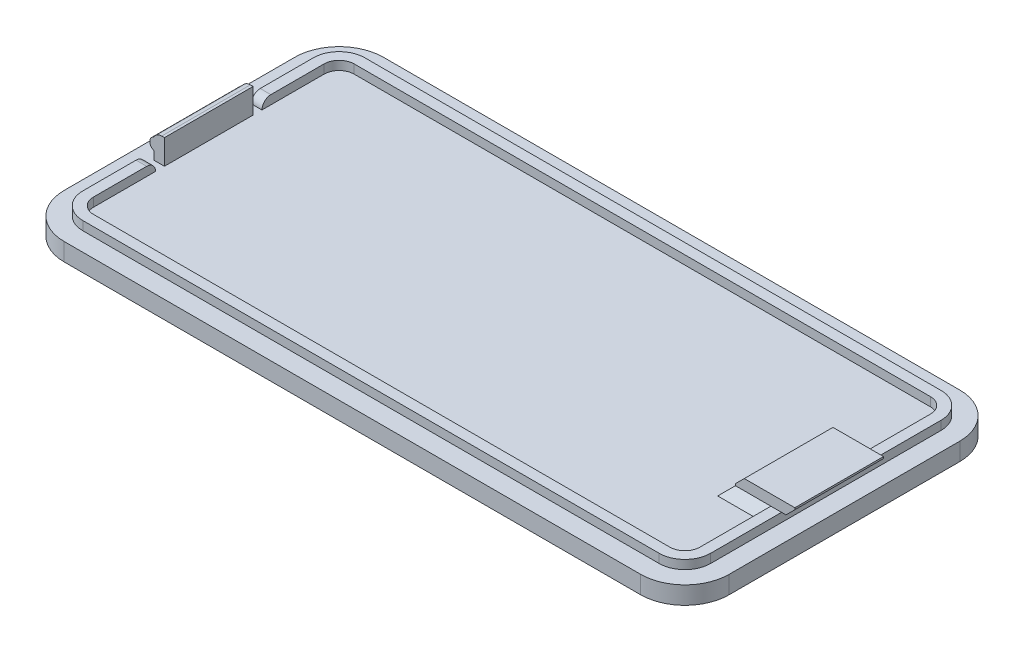
SolidWorks part; units mm, degrees
ref_plane "前视基准面" through (0, 0, 0) normal (0, 0, 1) x (1, 0, 0)
ref_plane "上视基准面" through (0, 0, 0) normal (0, 1, 0) x (1, 0, 0)
ref_plane "右视基准面" through (0, 0, 0) normal (1, 0, 0) x (0, 0, -1)
sketch "zero" plane through (0, 0, 0) normal (0, 1, 0) x (1, 0, 0)
  line L1 (-29.5, 15) -> (29.5, 15)
  line L2 (-32.5, 12) -> (-32.5, -12)
  line L3 (-29.5, -15) -> (29.5, -15)
  line L4 (32.5, 12) -> (32.5, -12)
  line L5 (-32.5, 15) -> (32.5, -15) construction
  line L6 (-32.5, -15) -> (32.5, 15) construction
  line L7 (-25.7, -15) -> (-14.5, -15)
  line L8 (-25.7, -15) -> (-25.7, -9.6569)
  line L9 (-25.7, -9.6569) -> (-14.5, -9.6569)
  line L10 (-14.5, -15) -> (-14.5, -9.6569)
  line L11 (5.2, -15) -> (12.7, -15)
  line L12 (5.2, -15) -> (5.2, -11)
  line L13 (5.2, -11) -> (12.7, -11)
  line L14 (12.7, -15) -> (12.7, -11)
  line L15 (17.8, -15) -> (25.3, -15)
  line L16 (17.8, -15) -> (17.8, -11)
  line L17 (17.8, -11) -> (25.3, -11)
  line L18 (25.3, -15) -> (25.3, -11)
  line L19 (-32.5, 7.7) -> (-19.5, 7.7)
  line L20 (-32.5, 7.7) -> (-32.5, -4.3)
  line L21 (-32.5, -4.3) -> (-19.5, -4.3)
  line L22 (-19.5, 7.7) -> (-19.5, -4.3)
  line L23 (-25.5, 14) -> (25.5, 14)
  line L24 (-25.5, 14) -> (-25.5, 8.8)
  line L25 (-25.5, 8.8) -> (25.5, 8.8)
  line L26 (25.5, 14) -> (25.5, 8.8)
  line L27 (-19.5, 7.2329) -> (-35.5, 7.2329)
  line L28 (-19.5, 7.2329) -> (-19.5, -3.7671)
  line L29 (-19.5, -3.7671) -> (-35.5, -3.7671)
  line L30 (-35.5, 7.2329) -> (-35.5, -3.7671)
  arc A0 (29.5, -15) -> (32.5, -12) centre (29.5, -12) ccw
  arc A1 (29.5, 15) -> (32.5, 12) centre (29.5, 12) cw
  arc A2 (-32.5, -12) -> (-29.5, -15) centre (-29.5, -12) ccw
  arc A3 (-29.5, 15) -> (-32.5, 12) centre (-29.5, 12) ccw
  circle A4 centre (-29, 11.4) radius 3
  circle A5 centre (-29, -11.5) radius 3
  circle A6 centre (29, 11.4) radius 3
  circle A7 centre (29, -11.5) radius 3
  circle A8 centre (-29, 11.4) radius 1.375
  circle A9 centre (-29, -11.5) radius 1.375
  circle A10 centre (29, -11.5) radius 1.375
  circle A11 centre (29, 11.4) radius 1.375
  point P0 (0, 0)
  dimension "D3" = 3
  dimension "D4" = 6
  dimension "D9" = 2.75
  dimension "D1" = 65
  dimension "D2" = 30
  dimension "D5" = 3.6
  dimension "D6" = 3.5
  dimension "D7" = 3.5
  dimension "D8" = 3.5
  dimension "D10" = 12
  dimension "D11" = 7.3
  dimension "D12" = 13
  dimension "D13" = 11.2
  dimension "D14" = 6.8
  dimension "D15" = 19.7
  dimension "D16" = 7.5
  dimension "D17" = 7.5
  dimension "D18" = 5.1
  dimension "D19" = 4
  dimension "D20" = 5.2
  dimension "D21" = 7
  dimension "D22" = 7
  dimension "D23" = 1
  dimension "D24" = 11
  dimension "D25" = 16
sketch "sugar" plane through (0, 0, 0) normal (0, 1, 0) x (1, 0, 0)
  line L1 (-29.5, 15) -> (29.5, 15)
  line L2 (-32.5, 12) -> (-32.5, -12)
  line L3 (-29.5, -15) -> (29.5, -15)
  line L4 (32.5, 12) -> (32.5, -12)
  line L5 (-32.5, 15) -> (32.5, -15) construction
  line L6 (-32.5, -15) -> (32.5, 15) construction
  line L7 (23.5, -11.5) -> (19.5, -11.5)
  line L8 (23.5, -11.5) -> (23.5, -13.9082)
  line L9 (23.5, -13.9082) -> (19.5, -13.9082)
  line L10 (19.5, -11.5) -> (19.5, -13.9082)
  line L11 (16, -11.0071) -> (8.5, -11.0071)
  line L12 (16, -11.0071) -> (16, -15)
  line L13 (16, -15) -> (8.5, -15)
  line L14 (8.5, -11.0071) -> (8.5, -15)
  line L15 (20.5, -13.9082) -> (22.5, -13.9082)
  line L16 (20.5, -13.9082) -> (20.5, -14.8173)
  line L17 (20.5, -14.8173) -> (22.5, -14.8173)
  line L18 (22.5, -13.9082) -> (22.5, -14.8173)
  arc A0 (29.5, 15) -> (32.5, 12) centre (29.5, 12) cw
  arc A1 (29.5, -15) -> (32.5, -12) centre (29.5, -12) ccw
  arc A2 (-32.5, -12) -> (-29.5, -15) centre (-29.5, -12) ccw
  arc A3 (-29.5, 15) -> (-32.5, 12) centre (-29.5, 12) ccw
  circle A4 centre (-29, 11.4) radius 3
  circle A5 centre (-29, 11.4) radius 1.375
  circle A6 centre (-29, -11.5) radius 3
  circle A7 centre (-29, -11.5) radius 1.375
  circle A8 centre (29, 11.4) radius 3
  circle A9 centre (29, 11.4) radius 1.375
  circle A10 centre (29, -11.5) radius 3
  circle A11 centre (29, -11.5) radius 1.375
  dimension "D3" = 3
  dimension "D1" = 65
  dimension "D2" = 30
  dimension "D4" = 9
  dimension "D5" = 4
  dimension "D6" = 3.5
  dimension "D7" = 7.5
  dimension "D8" = 2
  dimension "D9" = 1
sketch "case" plane through (0, 0, 0) normal (0, 1, 0) x (1, 0, 0)
  line L1 (-34.0422, 18) -> (30.9578, 18)
  line L2 (-39.0422, 13) -> (-39.0422, -13)
  line L3 (-34.0422, -18) -> (30.9578, -18)
  line L4 (35.9578, 13) -> (35.9578, -13)
  line L5 (-39.0422, 18) -> (35.9578, -18) construction
  line L6 (-39.0422, -18) -> (35.9578, 18) construction
  arc A0 (-39.0422, -13) -> (-34.0422, -18) centre (-34.0422, -13) ccw
  arc A1 (30.9578, -18) -> (35.9578, -13) centre (30.9578, -13) ccw
  arc A2 (30.9578, 18) -> (35.9578, 13) centre (30.9578, 13) cw
  arc A3 (-34.0422, 18) -> (-39.0422, 13) centre (-34.0422, 13) ccw
  point P0 (-1.5422, 0)
  point P3 (-1.5422, 0)
  dimension "D3" = 5
  dimension "D1" = 75
  dimension "D2" = 36
extrude "凸台-拉伸2" add sketch "case" along normal blind 2
sketch "草图2" plane through (0, 0, 0) normal (0, 1, 0) x (1, 0, 0)
  line L4 (-34.0422, -14.7) -> (30.9578, -14.7)
  line L5 (32.6578, -13) -> (32.6578, 13)
  line L6 (30.9578, 14.7) -> (-34.0422, 14.7)
  line L7 (-35.7422, 13) -> (-35.7422, -13)
  line L8 (33.8578, -13) -> (33.8578, 13)
  line L9 (30.9578, 15.9) -> (-34.0422, 15.9)
  line L10 (-36.9422, 13) -> (-36.9422, -13)
  line L11 (-34.0422, -15.9) -> (30.9578, -15.9)
  line L12 (33.8578, -13) -> (33.8578, 13)
  line L13 (30.9578, 15.9) -> (-34.0422, 15.9)
  line L14 (-36.9422, 13) -> (-36.9422, -13)
  line L15 (-34.0422, -15.9) -> (30.9578, -15.9)
  arc A4 (30.9578, -14.7) -> (32.6578, -13) centre (30.9578, -13) ccw
  arc A5 (32.6578, 13) -> (30.9578, 14.7) centre (30.9578, 13) ccw
  arc A6 (-34.0422, 14.7) -> (-35.7422, 13) centre (-34.0422, 13) ccw
  arc A7 (-35.7422, -13) -> (-34.0422, -14.7) centre (-34.0422, -13) ccw
  arc A8 (30.9578, -15.9) -> (33.8578, -13) centre (30.9578, -13) ccw
  arc A9 (33.8578, 13) -> (30.9578, 15.9) centre (30.9578, 13) ccw
  arc A10 (-34.0422, 15.9) -> (-36.9422, 13) centre (-34.0422, 13) ccw
  arc A11 (-36.9422, -13) -> (-34.0422, -15.9) centre (-34.0422, -13) ccw
  arc A12 (30.9578, -15.9) -> (33.8578, -13) centre (30.9578, -13) ccw
  arc A13 (33.8578, 13) -> (30.9578, 15.9) centre (30.9578, 13) ccw
  arc A14 (-34.0422, 15.9) -> (-36.9422, 13) centre (-34.0422, 13) ccw
  arc A15 (-36.9422, -13) -> (-34.0422, -15.9) centre (-34.0422, -13) ccw
  dimension "D1" = 2.1
  dimension "D2" = 1.2
ref_plane "基准面1" through (0, 2, 0) normal (0, 1, 0) x (1, 0, 0)
sketch "草图3" plane through (0, 2, 0) normal (0, 1, 0) x (1, 0, 0)
  line L4 (-34.0422, -14.7) -> (30.9578, -14.7)
  line L5 (32.6578, -13) -> (32.6578, 13)
  line L6 (30.9578, 14.7) -> (-34.0422, 14.7)
  line L7 (-35.7422, 13) -> (-35.7422, -13)
  line L8 (-34.0422, -14.7) -> (30.9578, -14.7)
  line L9 (32.6578, -13) -> (32.6578, 13)
  line L10 (30.9578, 14.7) -> (-34.0422, 14.7)
  line L11 (-35.7422, 13) -> (-35.7422, -13)
  line L12 (-36.9422, 13) -> (-36.9422, -13)
  line L13 (-34.0422, -15.9) -> (30.9578, -15.9)
  line L14 (33.8578, -13) -> (33.8578, 13)
  line L15 (30.9578, 15.9) -> (-34.0422, 15.9)
  line L16 (-36.9422, 13) -> (-36.9422, -13)
  line L17 (-34.0422, -15.9) -> (30.9578, -15.9)
  line L18 (33.8578, -13) -> (33.8578, 13)
  line L19 (30.9578, 15.9) -> (-34.0422, 15.9)
  arc A4 (30.9578, -14.7) -> (32.6578, -13) centre (30.9578, -13) ccw
  arc A5 (32.6578, 13) -> (30.9578, 14.7) centre (30.9578, 13) ccw
  arc A6 (-34.0422, 14.7) -> (-35.7422, 13) centre (-34.0422, 13) ccw
  arc A7 (-35.7422, -13) -> (-34.0422, -14.7) centre (-34.0422, -13) ccw
  arc A8 (30.9578, -14.7) -> (32.6578, -13) centre (30.9578, -13) ccw
  arc A9 (32.6578, 13) -> (30.9578, 14.7) centre (30.9578, 13) ccw
  arc A10 (-34.0422, 14.7) -> (-35.7422, 13) centre (-34.0422, 13) ccw
  arc A11 (-35.7422, -13) -> (-34.0422, -14.7) centre (-34.0422, -13) ccw
  arc A12 (-36.9422, -13) -> (-34.0422, -15.9) centre (-34.0422, -13) ccw
  arc A13 (30.9578, -15.9) -> (33.8578, -13) centre (30.9578, -13) ccw
  arc A14 (33.8578, 13) -> (30.9578, 15.9) centre (30.9578, 13) ccw
  arc A15 (-34.0422, 15.9) -> (-36.9422, 13) centre (-34.0422, 13) ccw
  arc A16 (-36.9422, -13) -> (-34.0422, -15.9) centre (-34.0422, -13) ccw
  arc A17 (30.9578, -15.9) -> (33.8578, -13) centre (30.9578, -13) ccw
  arc A18 (33.8578, 13) -> (30.9578, 15.9) centre (30.9578, 13) ccw
  arc A19 (-34.0422, 15.9) -> (-36.9422, 13) centre (-34.0422, 13) ccw
  dimension "D1" = 0
  dimension "D2" = 0
extrude "凸台-拉伸4" add sketch "草图3" along normal blind 1
sketch "草图5" plane through (0, 2, 0) normal (0, 1, 0) x (1, 0, 0)
  line L0 (32.6578, -13) -> (32.6578, 13) construction
  line L1 (28.6578, 5) -> (32.6578, 5)
  line L2 (28.6578, 5) -> (28.6578, -5)
  line L3 (28.6578, -5) -> (32.6578, -5)
  line L4 (32.6578, 5) -> (32.6578, -5)
  line L5 (28.6578, 5) -> (32.6578, -5) construction
  line L6 (28.6578, -5) -> (32.6578, 5) construction
  point P0 (30.6578, 0)
  dimension "D2" = 10
  dimension "D3" = 4
  dimension "D4" = 0
extrude "凸台-拉伸6" add sketch "草图5" along normal blind 2.2
ref_plane "基准面3" through (33.8578, 0, 0) normal (1, 0, 0) x (0, 0, -1)
ref_plane "基准面4" through (32.6578, 0, 0) normal (1, 0, 0) x (0, 0, -1)
sketch "草图6" plane through (32.6578, 0, 0) normal (1, 0, 0) x (0, 0, -1)
  line L1 (5, 4.2) -> (-5, 4.2)
  line L2 (5, 4.2) -> (5, 3)
  line L3 (5, 3) -> (-5, 3)
  line L4 (-5, 4.2) -> (-5, 3)
extrude "凸台-拉伸7" add sketch "草图6" along normal blind 2.7
chamfer "倒角1" distance 1 angle 45 1 edges at (35.3578, 3, 0)
chamfer "倒角2" distance 1 angle 45 3 edges at (30.6578, 2, 5) (28.6578, 2, 0) (30.6578, 2, -5)
chamfer "倒角3" distance 1 angle 45 1 edges at (28.6578, 4.2, 0)
sketch "草图7" plane through (0, 2, 0) normal (0, 1, 0) x (1, 0, 0)
  line L0 (-36.9422, 13) -> (-36.9422, -13) construction
  line L1 (-36.9422, 5) -> (-35.7422, 5)
  line L2 (-36.9422, 5) -> (-36.9422, -5)
  line L3 (-36.9422, -5) -> (-35.7422, -5)
  line L4 (-35.7422, 5) -> (-35.7422, -5)
  line L5 (-35.7422, 13) -> (-35.7422, -13) construction
  point P10 (-35.7422, 0)
  dimension "D1" = 5
  dimension "D2" = 10
extrude "凸台-拉伸8" add sketch "草图7" along normal blind 2.8
ref_plane "基准面5" through (0, 0, 5) normal (0, 0, 1) x (1, 0, 0)
sketch "草图8" plane through (0, 0, 5) normal (0, 0, 1) x (1, 0, 0)
  line L0 (-34.0422, 2) -> (-39.0422, 2) construction
  line L1 (-36.9422, 4.8) -> (-36.9422, 3) construction
  circle A0 centre (-36.6922, 3.6) radius 0.7
  dimension "D1" = 1.4
  dimension "D2" = 1.6
  dimension "D3" = 0.25
extrude "凸台-拉伸9" add sketch "草图8" against normal blind 10
fillet "圆角1" radius 1 1 edges at (-36.9422, 4.8, 0)
ref_plane "基准面7" through (-36.9422, 0, 0) normal (-1, 0, 0) x (0, 0, 1)
sketch "草图11" plane through (-36.9422, 0, 0) normal (-1, 0, 0) x (0, 0, 1)
  line L0 (-13, 2) -> (13, 2) construction
  line L1 (5, 3) -> (6, 3)
  line L2 (5, 3) -> (5, 2)
  line L3 (5, 2) -> (6, 2)
  line L4 (6, 3) -> (6, 2)
  line L6 (-5, 3) -> (-6, 3)
  line L7 (-5, 3) -> (-5, 2)
  line L8 (-5, 2) -> (-6, 2)
  line L9 (-6, 3) -> (-6, 2)
  dimension "D1" = 1
  dimension "D2" = 1
extrude "切除-拉伸1" cut sketch "草图11" against normal blind 1.2
fillet "圆角2" radius 1 2 edges at (-36.3422, 3, 6) (-36.3422, 3, -6)
ref_plane "基准面8" through (0, 0, 0) normal (0, -1, 0) x (-1, 0, 0)
sketch "草图12" plane through (0, 0, 0) normal (0, -1, 0) x (-1, 0, 0)
  line L76 (34.0422, -18) -> (-30.9578, -18) construction
  line L78 (39.0422, 13) -> (39.0422, -13) construction
  line B0 (-8.1993, 5.026) -> (-9.0198, 5.499)
  line B1 (-9.0198, 5.499) -> (-13.2767, 7.9551)
  line B2 (-13.2767, 7.9551) -> (-14.0973, 8.4339)
  line B3 (-15.8183, 8.4339) -> (-16.6389, 7.9551)
  line B4 (-16.6389, 7.9551) -> (-20.8958, 5.499)
  line B5 (-20.8958, 5.499) -> (-21.7165, 5.026)
  line B6 (-22.577, 3.5387) -> (-22.577, -3.2769)
  line B7 (-21.7165, -4.7643) -> (-20.8958, -5.2373)
  line B8 (-20.8958, -5.2373) -> (-16.6389, -7.6934)
  line B9 (-16.6389, -7.6934) -> (-15.8183, -8.172)
  line B10 (-14.0973, -8.172) -> (-13.2767, -7.6934)
  line B11 (-13.2767, -7.6934) -> (-9.0198, -5.2373)
  line B12 (-9.0198, -5.2373) -> (-8.1993, -4.7643)
  line B13 (-7.3388, -3.2769) -> (-7.3388, 3.5387)
  line B14 (-20.6223, 4.3479) -> (-15.3568, 7.391)
  line B15 (-14.5532, 7.391) -> (-9.3162, 4.3422)
  line B16 (-9.3105, 3.6413) -> (-14.3993, 0.5982)
  line B17 (-12.8208, -4.5591) -> (-13.4135, -4.8896)
  line B18 (-13.4705, -4.9865) -> (-13.4705, -6.6961)
  line B19 (-13.5274, -6.793) -> (-14.633, -7.4198)
  line B20 (-14.7983, -7.3229) -> (-14.7983, -2.046)
  line B21 (-14.7413, -1.9491) -> (-12.8607, -0.8835)
  line B22 (-8.9173, -4.2058) -> (-10.0114, -4.8269)
  line B23 (-10.1767, -4.7301) -> (-10.1767, -2.2169)
  line B24 (-10.1197, -2.1201) -> (-9.0256, -1.5046)
  line B25 (-8.8603, -1.6015) -> (-8.8603, -4.1089)
  line B26 (-12.8893, -3.5447) -> (-13.4135, -3.8069)
  line B27 (-13.4705, -3.6872) -> (-13.4705, -2.3423)
  line B28 (-13.4135, -2.2455) -> (-12.9234, -1.9719)
  line B29 (-3.344, 3.06) -> (-5.2189, 3.06)
  line B30 (-5.2189, 3.06) -> (-5.2189, -3.5048)
  line B31 (-5.2189, -3.5048) -> (-4.3868, -3.5048)
  line B32 (-4.3868, -3.5048) -> (-4.3868, -0.9005)
  line B33 (-4.3868, -0.9005) -> (-3.2984, -0.9005)
  line B34 (-3.4066, -0.2281) -> (-4.3868, -0.2281)
  line B35 (-4.3868, -0.2281) -> (-4.3868, 2.3876)
  line B36 (-4.3868, 2.3876) -> (-3.4408, 2.3876)
  line B37 (0.1948, 1.3618) -> (0.1948, -3.5048)
  line B38 (0.1948, -3.5048) -> (1.0098, -3.5048)
  line B39 (1.0098, -3.5048) -> (1.0098, 1.3618)
  line B40 (1.0098, 1.3618) -> (0.1948, 1.3618)
  line B41 (5.7169, 0.2847) -> (4.8849, 0.6153)
  line B42 (6.0417, 1.4017) -> (6.8396, 2.4047)
  line B43 (3.6084, -0.5586) -> (4.4575, -0.9177)
  line B44 (2.9074, -1.5673) -> (2.0014, -2.6729)
  line B45 (10.8229, 1.5898) -> (10.8229, -1.7497)
  line B46 (9.3811, -1.3621) -> (9.3811, 1.5898)
  line B47 (9.3811, 1.5898) -> (7.7912, 1.5898)
  line B48 (7.7912, 1.5898) -> (7.7912, -1.5616)
  line B49 (10.9711, -2.8039) -> (11.0052, -2.8039)
  line B50 (11.0052, -2.8039) -> (11.1193, -3.5048)
  line B51 (11.1193, -3.5048) -> (12.4185, -3.5048)
  line B52 (12.4185, -3.5048) -> (12.4185, 1.5898)
  line B53 (12.4185, 1.5898) -> (10.8229, 1.5898)
  line B54 (16.2708, -2.5019) -> (15.4673, -2.5019)
  line B55 (17.365, 0.4386) -> (18.1513, 0.4386)
  line B56 (18.1513, 0.4386) -> (18.1513, 1.5898)
  line B57 (18.1513, 1.5898) -> (16.2822, 1.5898)
  line B58 (14.0312, -1.4533) -> (14.0312, -1.4875)
  line B59 (13.9344, -3.3168) -> (13.9344, -3.3624)
  line B60 (15.4844, -3.7214) -> (15.9688, -3.7214)
  line B61 (18.6072, 1.0484) -> (19.1657, -0.0002)
  line B62 (21.411, -2.992) -> (21.4508, -2.992)
  line B63 (21.4508, -2.992) -> (21.5648, -3.5048)
  line B64 (21.5648, -3.5048) -> (22.8641, -3.5048)
  line B65 (22.8641, -3.5048) -> (22.8641, -0.6099)
  line B66 (21.2685, -1.1741) -> (21.2685, -1.989)
  line B67 (25.3545, 0.7065) -> (25.3203, 0.7065)
  line B68 (25.3203, 0.7065) -> (25.212, 1.5898)
  line B69 (25.212, 1.5898) -> (23.9127, 1.5898)
  line B70 (23.9127, 1.5898) -> (23.9127, -3.5048)
  line B71 (23.9127, -3.5048) -> (25.4969, -3.5048)
  line B72 (25.4969, -3.5048) -> (25.4969, -0.5928)
  line B73 (27.1552, 0.2392) -> (27.423, 1.6125)
  line B74 (-13.4135, -3.8069) -> (-13.4135, -4.8896)
  line B75 (-13.4705, -3.6872) -> (-13.4705, -4.9865)
  spline B76 degree 3 poles (-14.0973, 8.4339) (-14.3652, 8.582) (-14.6615, 8.6618) (-14.9578, 8.6618) knots 3 3 3 3 4 4 4 4
  spline B77 degree 3 poles (-14.9578, 8.6618) (-15.2541, 8.6618) (-15.5505, 8.582) (-15.8183, 8.4339) knots 4 4 4 4 5 5 5 5
  spline B78 degree 3 poles (-21.7165, 5.026) (-22.2464, 4.7183) (-22.577, 4.1485) (-22.577, 3.5387) knots 8 8 8 8 9 9 9 9
  spline B79 degree 3 poles (-22.577, -3.2769) (-22.577, -3.8923) (-22.2464, -4.4565) (-21.7165, -4.7643) knots 10 10 10 10 11 11 11 11
  spline B80 degree 3 poles (-15.8183, -8.172) (-15.5505, -8.3259) (-15.2541, -8.4) (-14.9578, -8.4) knots 14 14 14 14 15 15 15 15
  spline B81 degree 3 poles (-14.9578, -8.4) (-14.6615, -8.4) (-14.3652, -8.3259) (-14.0973, -8.172) knots 15 15 15 15 16 16 16 16
  spline B82 degree 3 poles (-8.1993, -4.7643) (-7.6636, -4.4565) (-7.3388, -3.8923) (-7.3388, -3.2769) knots 19 19 19 19 20 20 20 20
  spline B83 degree 3 poles (-7.3388, 3.5387) (-7.3388, 4.1485) (-7.6636, 4.7183) (-8.1993, 5.026) knots 21 21 21 21 22 22 22 22
  spline B84 degree 2 poles (-15.5106, 0.5982) (-20.6622, 3.5729) (-20.6736, 3.5786) knots 0 0 0 1 1 1
  spline B85 degree 3 poles (-20.6736, 3.5786) (-20.9414, 3.7723) (-20.9129, 4.1826) (-20.6223, 4.3479) knots 1 1 1 1 2 2 2 2
  spline B86 degree 3 poles (-15.3568, 7.391) (-15.1117, 7.5335) (-14.8039, 7.5335) (-14.5532, 7.391) knots 3 3 3 3 4 4 4 4
  spline B87 degree 3 poles (-9.3162, 4.3422) (-9.0484, 4.1883) (-9.0427, 3.8008) (-9.3105, 3.6413) knots 5 5 5 5 6 6 6 6
  spline B88 degree 3 poles (-14.3993, 0.5982) (-14.7413, 0.3987) (-15.1687, 0.3987) (-15.5106, 0.5982) knots 7 7 7 7 8 8 8 8
  spline B89 degree 3 poles (-13.4705, -6.6961) (-13.4705, -6.736) (-13.4876, -6.7702) (-13.5274, -6.793) knots 3 3 3 3 4 4 4 4
  spline B90 degree 3 poles (-14.633, -7.4198) (-14.7071, -7.4597) (-14.7983, -7.4084) (-14.7983, -7.3229) knots 5 5 5 5 6 6 6 6
  spline B91 degree 3 poles (-14.7983, -2.046) (-14.7983, -2.0061) (-14.7812, -1.9662) (-14.7413, -1.9491) knots 7 7 7 7 8 8 8 8
  spline B92 degree 3 poles (-12.8607, -0.8835) (-11.6412, -0.1939) (-10.6326, -0.0572) (-10.6326, -1.4249) knots 9 9 9 9 10 10 10 10
  spline B93 degree 3 poles (-10.6326, -1.4249) (-10.6326, -2.7412) (-11.6526, -3.898) (-12.8208, -4.5591) knots 10 10 10 10 11 11 11 11
  spline B94 degree 3 poles (-8.8603, -4.1089) (-8.8603, -4.1488) (-8.8831, -4.1887) (-8.9173, -4.2058) knots 0 0 0 0 1 1 1 1
  spline B95 degree 3 poles (-10.0114, -4.8269) (-10.0855, -4.8668) (-10.1767, -4.8155) (-10.1767, -4.7301) knots 2 2 2 2 3 3 3 3
  spline B96 degree 3 poles (-10.1767, -2.2169) (-10.1767, -2.1771) (-10.1539, -2.1429) (-10.1197, -2.1201) knots 4 4 4 4 5 5 5 5
  spline B97 degree 3 poles (-9.0256, -1.5046) (-8.9515, -1.4647) (-8.8603, -1.516) (-8.8603, -1.6015) knots 6 6 6 6 7 7 7 7
  spline B98 degree 3 poles (-9.5156, 0.1651) (-9.0768, 0.4158) (-8.7634, 0.3076) (-8.7634, -0.0914) (-8.7634, -0.4846) (-9.0768, -0.9461) (-9.5156, -1.1912) knots 2 2 2 2 3 3 3 4 4 4 4
  spline B99 degree 3 poles (-9.5156, -1.1912) (-9.9601, -1.4476) (-10.2735, -1.3394) (-10.2735, -0.9461) (-10.2735, -0.5415) (-9.9601, -0.0856) (-9.5156, 0.1651) knots 0 0 0 0 1 1 1 2 2 2 2
  spline B100 degree 3 poles (-11.9319, -2.16) (-11.9319, -2.7013) (-12.2395, -3.18) (-12.8893, -3.5447) knots 0 0 0 0 1 1 1 1
  spline B101 degree 3 poles (-13.4705, -2.3423) (-13.4705, -2.3024) (-13.4477, -2.2625) (-13.4135, -2.2455) knots 4 4 4 4 5 5 5 5
  spline B102 degree 3 poles (-12.9234, -1.9719) (-12.2852, -1.6072) (-11.9319, -1.6015) (-11.9319, -2.16) knots 6 6 6 6 7 7 7 7
  spline B103 degree 3 poles (-3.2984, -0.9005) (-1.868, -0.9005) (-0.8822, -0.2509) (-0.8822, 1.1339) knots 5 5 5 5 6 6 6 6
  spline B104 degree 3 poles (-0.8822, 1.1339) (-0.8822, 2.5699) (-1.868, 3.06) (-3.344, 3.06) knots 6 6 6 6 7 7 7 7
  spline B105 degree 3 poles (-3.4408, 2.3876) (-2.2897, 2.3876) (-1.7084, 2.0855) (-1.7084, 1.1339) knots 3 3 3 3 4 4 4 4
  spline B106 degree 3 poles (-1.7084, 1.1339) (-1.7084, 0.1936) (-2.2498, -0.2281) (-3.4066, -0.2281) knots 4 4 4 4 5 5 5 5
  spline B107 degree 3 poles (0.6052, 2.3648) (0.93, 2.3648) (1.1694, 2.587) (1.1694, 2.889) (1.1694, 3.2253) (0.93, 3.419) (0.6052, 3.419) knots 2 2 2 2 3 3 3 4 4 4 4
  spline B108 degree 3 poles (0.6052, 3.419) (0.2804, 3.419) (0.041, 3.2253) (0.041, 2.889) (0.041, 2.587) (0.2804, 2.3648) (0.6052, 2.3648) knots 0 0 0 0 1 1 1 2 2 2 2
  spline B109 degree 3 poles (4.8849, 0.6153) (4.2979, 0.8489) (3.8762, 0.9914) (3.8762, 1.3618) knots 1 1 1 1 2 2 2 2
  spline B110 degree 3 poles (3.8762, 1.3618) (3.8762, 1.7151) (4.1783, 1.9146) (4.674, 1.9146) knots 2 2 2 2 3 3 3 3
  spline B111 degree 3 poles (4.674, 1.9146) (5.1926, 1.9146) (5.6029, 1.7379) (6.0417, 1.4017) knots 3 3 3 3 4 4 4 4
  spline B112 degree 3 poles (6.8396, 2.4047) (6.2583, 2.9916) (5.4433, 3.2879) (4.674, 3.2879) knots 5 5 5 5 6 6 6 6
  spline B113 degree 3 poles (4.674, 3.2879) (3.2551, 3.2879) (2.2521, 2.3876) (2.2521, 1.2706) knots 6 6 6 6 7 7 7 7
  spline B114 degree 3 poles (2.2521, 1.2706) (2.2521, 0.3019) (2.9074, -0.2794) (3.6084, -0.5586) knots 7 7 7 7 8 8 8 8
  spline B115 degree 3 poles (4.4575, -0.9177) (5.0274, -1.157) (5.3978, -1.2824) (5.3978, -1.6699) knots 9 9 9 9 10 10 10 10
  spline B116 degree 3 poles (5.3978, -1.6699) (5.3978, -2.0289) (5.1185, -2.2511) (4.5259, -2.2511) knots 10 10 10 10 11 11 11 11
  spline B117 degree 3 poles (4.5259, -2.2511) (4.0016, -2.2511) (3.3804, -1.9719) (2.9074, -1.5673) knots 11 11 11 11 12 12 12 12
  spline B118 degree 3 poles (2.0014, -2.6729) (2.6909, -3.3054) (3.6254, -3.6302) (4.4916, -3.6302) knots 13 13 13 13 14 14 14 14
  spline B119 degree 3 poles (4.4916, -3.6302) (6.1044, -3.6302) (7.0389, -2.6557) (7.0389, -1.5445) knots 14 14 14 14 15 15 15 15
  spline B120 degree 3 poles (7.0389, -1.5445) (7.0389, -0.6042) (6.5432, -0.0458) (5.7169, 0.2847) knots 15 15 15 15 16 16 16 16
  spline B121 degree 3 poles (10.8229, -1.7497) (10.5551, -2.1258) (10.3328, -2.2682) (9.9738, -2.2682) knots 1 1 1 1 2 2 2 2
  spline B122 degree 3 poles (9.9738, -2.2682) (9.5692, -2.2682) (9.3811, -2.0688) (9.3811, -1.3621) knots 2 2 2 2 3 3 3 3
  spline B123 degree 3 poles (7.7912, -1.5616) (7.7912, -2.8324) (8.2642, -3.6302) (9.3754, -3.6302) knots 6 6 6 6 7 7 7 7
  spline B124 degree 3 poles (9.3754, -3.6302) (10.0706, -3.6302) (10.5494, -3.3054) (10.9711, -2.8039) knots 7 7 7 7 8 8 8 8
  spline B125 degree 3 poles (15.4673, -2.5019) (14.9202, -2.5019) (14.7151, -2.3936) (14.7151, -2.16) knots 1 1 1 1 2 2 2 2
  spline B126 degree 3 poles (14.7151, -2.16) (14.7151, -1.989) (14.7549, -1.9092) (14.8746, -1.8009) knots 2 2 2 2 3 3 3 3
  spline B127 degree 3 poles (14.8746, -1.8009) (15.0969, -1.8636) (15.302, -1.8921) (15.473, -1.8921) knots 3 3 3 3 4 4 4 4
  spline B128 degree 3 poles (15.473, -1.8921) (16.6013, -1.8921) (17.5074, -1.3735) (17.5074, -0.1825) knots 4 4 4 4 5 5 5 5
  spline B129 degree 3 poles (17.5074, -0.1825) (17.5074, 0.0625) (17.4447, 0.2962) (17.365, 0.4386) knots 5 5 5 5 6 6 6 6
  spline B130 degree 3 poles (16.2822, 1.5898) (16.0485, 1.6752) (15.7693, 1.7151) (15.473, 1.7151) knots 9 9 9 9 10 10 10 10
  spline B131 degree 3 poles (15.473, 1.7151) (14.3732, 1.7151) (13.3417, 1.1111) (13.3417, -0.1369) knots 10 10 10 10 11 11 11 11
  spline B132 degree 3 poles (13.3417, -0.1369) (13.3417, -0.7296) (13.6722, -1.2026) (14.0312, -1.4533) knots 11 11 11 11 12 12 12 12
  spline B133 degree 3 poles (14.0312, -1.4875) (13.7007, -1.7212) (13.467, -2.0802) (13.467, -2.4392) knots 13 13 13 13 14 14 14 14
  spline B134 degree 3 poles (13.467, -2.4392) (13.467, -2.8666) (13.6665, -3.1344) (13.9344, -3.3168) knots 14 14 14 14 15 15 15 15
  spline B135 degree 3 poles (13.9344, -3.3624) (13.4613, -3.6017) (13.2106, -3.9436) (13.2106, -4.3653) knots 16 16 16 16 17 17 17 17
  spline B136 degree 3 poles (13.2106, -4.3653) (13.2106, -5.2771) (14.1737, -5.6475) (15.3476, -5.6475) knots 17 17 17 17 18 18 18 18
  spline B137 degree 3 poles (15.3476, -5.6475) (17.1199, -5.6475) (18.2312, -4.8839) (18.2312, -3.8069) knots 18 18 18 18 19 19 19 19
  spline B138 degree 3 poles (18.2312, -3.8069) (18.2312, -2.8837) (17.5245, -2.5019) (16.2708, -2.5019) knots 19 19 19 19 20 20 20 20
  spline B139 degree 3 poles (15.473, -0.9347) (15.1083, -0.9347) (14.8291, -0.6669) (14.8291, -0.1369) (14.8291, 0.3816) (15.1083, 0.6495) (15.473, 0.6495) knots 2 2 2 2 3 3 3 4 4 4 4
  spline B140 degree 3 poles (15.473, 0.6495) (15.8491, 0.6495) (16.1169, 0.3816) (16.1169, -0.1369) (16.1169, -0.6669) (15.8491, -0.9347) (15.473, -0.9347) knots 0 0 0 0 1 1 1 2 2 2 2
  spline B141 degree 3 poles (15.5983, -4.6503) (14.943, -4.6503) (14.5156, -4.4736) (14.5156, -4.1146) knots 0 0 0 0 1 1 1 1
  spline B142 degree 3 poles (14.5156, -4.1146) (14.5156, -3.9436) (14.5953, -3.8012) (14.7549, -3.6587) knots 1 1 1 1 2 2 2 2
  spline B143 degree 3 poles (14.7549, -3.6587) (14.9202, -3.7043) (15.114, -3.7214) (15.4844, -3.7214) knots 2 2 2 2 3 3 3 3
  spline B144 degree 3 poles (15.9688, -3.7214) (16.4417, -3.7214) (16.7096, -3.7841) (16.7096, -4.0861) knots 4 4 4 4 5 5 5 5
  spline B145 degree 3 poles (16.7096, -4.0861) (16.7096, -4.4109) (16.2537, -4.6503) (15.5983, -4.6503) knots 5 5 5 5 6 6 6 6
  spline B146 degree 3 poles (20.8013, 1.7151) (20.0091, 1.7151) (19.2797, 1.4473) (18.6072, 1.0484) knots 0 0 0 0 1 1 1 1
  spline B147 degree 3 poles (19.1657, -0.0002) (19.6729, 0.2847) (20.0946, 0.4443) (20.4992, 0.4443) knots 2 2 2 2 3 3 3 3
  spline B148 degree 3 poles (20.4992, 0.4443) (21.0177, 0.4443) (21.2344, 0.205) (21.2685, -0.2053) knots 3 3 3 3 4 4 4 4
  spline B149 degree 3 poles (21.2685, -0.2053) (19.2797, -0.4219) (18.4362, -1.0031) (18.4362, -2.0802) knots 4 4 4 4 5 5 5 5
  spline B150 degree 3 poles (18.4362, -2.0802) (18.4362, -2.9293) (19.0118, -3.6302) (19.9522, -3.6302) knots 5 5 5 5 6 6 6 6
  spline B151 degree 3 poles (19.9522, -3.6302) (20.5163, -3.6302) (20.9893, -3.3681) (21.411, -2.992) knots 6 6 6 6 7 7 7 7
  spline B152 degree 3 poles (22.8641, -0.6099) (22.8641, 0.9857) (22.1176, 1.7151) (20.8013, 1.7151) knots 11 11 11 11 12 12 12 12
  spline B153 degree 3 poles (21.2685, -1.989) (21.0349, -2.2398) (20.824, -2.3936) (20.4992, -2.3936) knots 0 0 0 0 1 1 1 1
  spline B154 degree 3 poles (20.4992, -2.3936) (20.1686, -2.3936) (19.9522, -2.2511) (19.9522, -1.9548) knots 1 1 1 1 2 2 2 2
  spline B155 degree 3 poles (19.9522, -1.9548) (19.9522, -1.5958) (20.277, -1.3109) (21.2685, -1.1741) knots 2 2 2 2 3 3 3 3
  spline B156 degree 3 poles (26.8076, 1.7151) (26.2947, 1.7151) (25.7305, 1.3846) (25.3545, 0.7065) knots 0 0 0 0 1 1 1 1
  spline B157 degree 3 poles (25.4969, -0.5928) (25.7648, 0.0796) (26.2207, 0.3189) (26.5967, 0.3189) knots 7 7 7 7 8 8 8 8
  spline B158 degree 3 poles (26.5967, 0.3189) (26.8247, 0.3189) (26.9729, 0.2847) (27.1552, 0.2392) knots 8 8 8 8 9 9 9 9
  spline B159 degree 3 poles (27.423, 1.6125) (27.2806, 1.6752) (27.1096, 1.7151) (26.8076, 1.7151) knots 10 10 10 10 11 11 11 11
  dimension "D1" = 9.6
  dimension "D2" = 54
sketch_block_instance "块1-1"
sketch_block "块1"
extrude "切除-拉伸2" cut sketch "草图12" against normal blind 0.5
